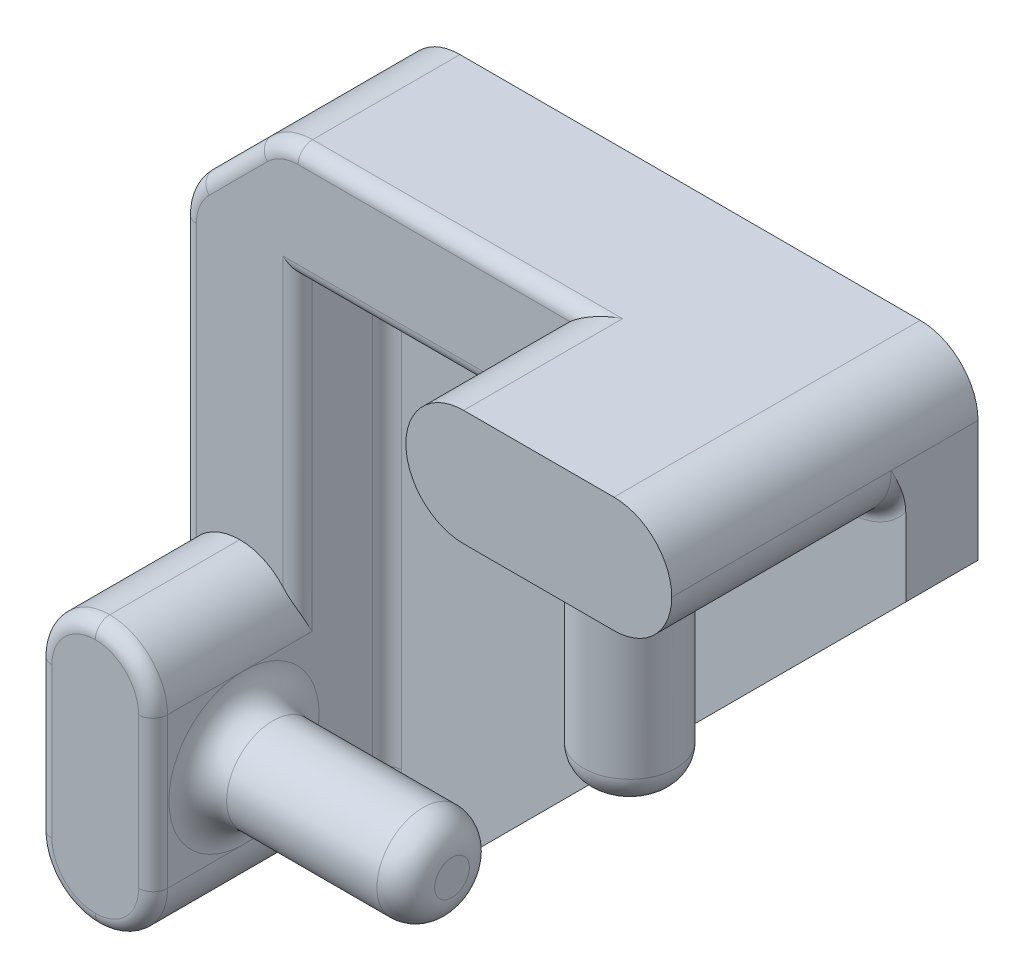
SolidWorks part; units mm, degrees
ref_plane "Plano frontal" through (0, 0, 0) normal (0, 0, 1) x (1, 0, 0)
ref_plane "Plano superior" through (0, 0, 0) normal (0, 1, 0) x (1, 0, 0)
ref_plane "Plano direito" through (0, 0, 0) normal (1, 0, 0) x (0, 0, -1)
sketch "Esboço1" plane through (0, 0, 0) normal (0, 0, 1) x (1, 0, 0)
  line L107 (-13.25, 6.5637) -> (-13.25, -11.25)
  line L117 (-11.25, -13.25) -> (-2.5074, -13.25)
  line L118 (-2.5074, -13.25) -> (13.25, 2.5074)
  line L119 (13.25, 2.5074) -> (13.25, 11.25)
  line L129 (11.25, 13.25) -> (-6.5637, 13.25)
  line L135 (-7.9779, 12.6642) -> (-12.6642, 7.9779)
  circle A0 centre (0, 0) radius 1.7
  arc A1 (13.25, 11.25) -> (11.25, 13.25) centre (11.25, 11.25) ccw
  arc A2 (-6.5637, 13.25) -> (-7.9779, 12.6642) centre (-6.5637, 11.25) ccw
  arc A3 (-12.6642, 7.9779) -> (-13.25, 6.5637) centre (-11.25, 6.5637) ccw
  arc A4 (-13.25, -11.25) -> (-11.25, -13.25) centre (-11.25, -11.25) ccw
  point P23 (-13.25, -13.25)
  dimension "D1" = 3.4
  dimension "D7" = 2
  dimension "D2" = 7.5962
  dimension "D3" = 135
  dimension "D4" = 22.1924
  dimension "D5" = 26.5
  dimension "D6" = 26.5
  dimension "D8" = 10.7426
  dimension "D9" = 13.25
extrude "Ressalto-extrusão1" add sketch "Esboço1" along normal blind 2.5 contours L135 L107 A1 A2 L117 L118 L119 A3 A4 L129 A0 region at (-1.4497, 1.4497, 0)
ref_plane "Plano1" through (0, 0, 2.5) normal (0, 0, -1) x (-1, 0, 0)
sketch "Esboço5" plane through (0, 0, 2.5) normal (0, 0, -1) x (-1, 0, 0)
  line L0 (-11.25, 4.7) -> (4.7, 4.7)
  line L1 (11.25, -13.25) -> (2.5074, -13.25) construction
  line L2 (4.7, 4.7) -> (4.7, -11.25)
  line L3 (-13.25, 2.5074) -> (-13.25, 11.25) construction
  line L4 (-11.25, 13.25) -> (6.5637, 13.25) construction
  line L5 (13.25, 6.5637) -> (13.25, -11.25) construction
  line L6 (7.9779, 12.6642) -> (12.6642, 7.9779) construction
  line L7 (-13.25, 6.7) -> (-13.25, 11.25)
  line L8 (-11.25, 13.25) -> (6.5637, 13.25)
  line L9 (7.9779, 12.6642) -> (12.6642, 7.9779)
  line L10 (13.25, 6.5637) -> (13.25, -11.25)
  line L11 (11.25, -13.25) -> (6.7, -13.25)
  arc A0 (7.9779, 12.6642) -> (6.5637, 13.25) centre (6.5637, 11.25) ccw construction
  arc A1 (11.25, -13.25) -> (13.25, -11.25) centre (11.25, -11.25) ccw
  arc A2 (13.25, 6.5637) -> (12.6642, 7.9779) centre (11.25, 6.5637) ccw
  arc A3 (7.9779, 12.6642) -> (6.5637, 13.25) centre (6.5637, 11.25) ccw
  arc A8 (4.7, -11.25) -> (6.7, -13.25) centre (6.7, -11.25) ccw
  arc A9 (-11.25, 4.7) -> (-13.25, 6.7) centre (-11.25, 6.7) cw
  arc A10 (-11.25, 13.25) -> (-13.25, 11.25) centre (-11.25, 11.25) ccw
  point P19 (4.7, -13.25)
  point P22 (-13.25, 4.7)
  dimension "D3" = 2
  dimension "D1" = 8.55
  dimension "D2" = 8.55
extrude "Ressalto-extrusão3" add sketch "Esboço5" against normal blind 3.1
sketch "Esboço6" plane through (0, 0, 5.6) normal (0, 0, 1) x (1, 0, 0)
  line L0 (-6.7, -4.05) -> (-11.25, -4.05)
  line L1 (-4.7, 4.7) -> (-4.7, -11.25) construction
  line L2 (-13.25, -11.25) -> (-13.25, 6.5637) construction
  line L3 (-6.7, -13.25) -> (-11.25, -13.25) construction
  line L4 (4.05, 6.7) -> (4.05, 11.25)
  line L5 (11.25, 4.7) -> (-4.7, 4.7) construction
  line L6 (-6.5637, 13.25) -> (11.25, 13.25) construction
  line L7 (13.25, 11.25) -> (13.25, 6.7) construction
  line L15 (-4.7, -11.25) -> (-4.7, 4.7)
  line L16 (-4.7, 4.7) -> (11.25, 4.7)
  line L17 (13.25, 6.7) -> (13.25, 11.25)
  line L18 (11.25, 13.25) -> (-6.5637, 13.25)
  line L19 (-7.9779, 12.6642) -> (-12.6642, 7.9779)
  line L20 (-13.25, 6.5637) -> (-13.25, -11.25)
  line L21 (-11.25, -13.25) -> (-6.7, -13.25)
  line L22 (-4.7, -11.25) -> (-4.7, -6.05)
  line L23 (6.05, 4.7) -> (11.25, 4.7)
  line L24 (13.25, 6.7) -> (13.25, 11.25)
  line L25 (11.25, 13.25) -> (6.05, 13.25)
  line L27 (-13.25, -6.05) -> (-13.25, -11.25)
  line L28 (-11.25, -13.25) -> (-6.7, -13.25)
  arc A0 (4.05, 11.25) -> (6.05, 13.25) centre (6.05, 11.25) cw
  arc A1 (4.05, 6.7) -> (6.05, 4.7) centre (6.05, 6.7) ccw
  arc A2 (-6.7, -4.05) -> (-4.7, -6.05) centre (-6.7, -6.05) cw
  arc A3 (-11.25, -4.05) -> (-13.25, -6.05) centre (-11.25, -6.05) ccw
  arc A6 (11.25, 4.7) -> (13.25, 6.7) centre (11.25, 6.7) ccw
  arc A7 (13.25, 11.25) -> (11.25, 13.25) centre (11.25, 11.25) ccw
  arc A8 (-6.5637, 13.25) -> (-7.9779, 12.6642) centre (-6.5637, 11.25) ccw
  arc A9 (-12.6642, 7.9779) -> (-13.25, 6.5637) centre (-11.25, 6.5637) ccw
  arc A10 (-13.25, -11.25) -> (-11.25, -13.25) centre (-11.25, -11.25) ccw
  arc A11 (-6.7, -13.25) -> (-4.7, -11.25) centre (-6.7, -11.25) ccw
  arc A12 (11.25, 4.7) -> (13.25, 6.7) centre (11.25, 6.7) ccw
  arc A13 (13.25, 11.25) -> (11.25, 13.25) centre (11.25, 11.25) ccw
  arc A16 (-13.25, -11.25) -> (-11.25, -13.25) centre (-11.25, -11.25) ccw
  arc A17 (-6.7, -13.25) -> (-4.7, -11.25) centre (-6.7, -11.25) ccw
  point P23 (4.05, 13.25)
  point P32 (4.05, 4.7)
  point P43 (-4.7, -4.05)
  point P46 (-13.25, -4.05)
  dimension "D4" = 2
  dimension "D1" = 9.2
  dimension "D2" = 9.2
  dimension "D3" = 0
extrude "Ressalto-extrusão4" add sketch "Esboço6" along normal blind 5
sketch "Esboço7" plane through (-4.7, 0, 0) normal (1, 0, 0) x (0, 0, -1)
  line L0 (-2.5, -8.65) -> (-5.854, -8.65) construction
  line L3 (-2.5, 4.7) -> (-2.5, -11.25) construction
  circle A0 centre (-7.454, -8.65) radius 1.6
  dimension "D1" = 3.2
  dimension "D2" = 3.354
extrude "Corte-extrusão3" [suppressed] cut sketch "Esboço7" against normal through all
ref_plane "Plano2" through (0, 0, 0) normal (-0.7071, -0.7071, 0) x (-0.7071, 0.7071, 0)
mirror "Espelhar1" [suppressed] about plane through (0, 0, 0) normal (-0.7071, -0.7071, 0)
sketch "Esboço11" plane through (0, 0, 5.6) normal (0, 0, 1) x (1, 0, 0)
  line L61 (-8.7, -13.25) -> (-8.7, 4.679)
  line L62 (-8.1142, 6.0932) -> (-6.0932, 8.1142)
  line L63 (-4.679, 8.7) -> (13.25, 8.7)
  line L64 (-12.6642, 7.9779) -> (-7.9779, 12.6642) construction
  line L67 (-11.25, -13.25) -> (-6.7, -13.25) construction
  line L68 (13.25, 6.7) -> (13.25, 11.25) construction
  line L69 (13.25, 8.7) -> (13.25, 14.8842)
  line L70 (13.25, 14.8842) -> (-15.6971, 14.8842)
  line L71 (-15.6971, 14.8842) -> (-15.6971, -13.25)
  line L72 (-15.6971, -13.25) -> (-8.7, -13.25)
  line L73 (-4.7, 4.7) -> (-4.7, -6.05) construction
  line L74 (6.05, 4.7) -> (-4.7, 4.7) construction
  arc A28 (-6.0932, 8.1142) -> (-4.679, 8.7) centre (-4.679, 6.7) cw
  arc A29 (-8.7, 4.679) -> (-8.1142, 6.0932) centre (-6.7, 4.679) cw
  dimension "D4" = 2
  dimension "D1" = 4
  dimension "D2" = 4
  dimension "D3" = 4.55
extrude "Corte-extrusão5" cut sketch "Esboço11" against normal through all both and the other way through all
fillet "Filete5" radius 2 4 edges at (4.05, 8.7, 8.1) (-8.7, -4.05, 8.1) (-8.7, -13.25, 5.3) (13.25, 8.7, 5.3)
fillet "Filete3" radius 0.5 17 edges at (12.6642, 5.2858, 2.5) (-5.2858, -12.6642, 2.5) (-5.2858, -12.6642, 10.6) (-5.2858, -4.6358, 10.6) (3.275, 4.7, 2.5) (-4.7, -3.275, 2.5) (-4.7, -0.675, 5.6) (0.675, 4.7, 5.6) (-4.7, -8.65, 10.6) (-8.1142, -12.6642, 10.6) (-8.7, -8.65, 10.6) (-8.1142, -4.6358, 10.6) (0.6855, 8.7, 5.6) (-5.4444, 8.5478, 5.6) (-7.1037, 7.1037, 5.6) (-8.5478, 5.4444, 5.6) (-8.7, -0.6855, 5.6)
ref_plane "Plano3" through (-6.7, 0, 0) normal (1, 0, 0) x (0, 0, -1)
sketch "Esboço10" [suppressed] plane through (-8.975, 0, 0) normal (1, 0, 0) x (0, 0, -1)
  line L0 (-9.0994, -5.8) -> (-13.6026, -5.8)
  line L1 (-4.1631, -8.65) -> (-5.8086, -5.8)
  line L2 (-5.8086, -5.8) -> (-9.0994, -5.8)
  line L3 (-9.0994, -5.8) -> (-10.7449, -8.65) construction
  line L4 (-10.7449, -8.65) -> (-9.0994, -11.5) construction
  line L5 (-9.0994, -11.5) -> (-5.8086, -11.5)
  line L6 (-5.8086, -11.5) -> (-4.1631, -8.65)
  line L7 (-13.6026, -5.8) -> (-13.6026, -11.5)
  line L8 (-13.6026, -11.5) -> (-9.0994, -11.5)
  circle A0 centre (-7.454, -8.65) radius 2.85 construction
  dimension "D1" = 5.7
  dimension "D2" = 4.5031
extrude "Corte-extrusão4" [suppressed] cut sketch "Esboço10" against normal mid plane 2.7
mirror "Espelhar2" [suppressed] about plane through (0, 0, 0) normal (-0.7071, -0.7071, 0)
extrude "Ressalto-extrusão5" add sketch "Esboço7<2>" along normal blind 7.2
sketch "Esboço7<2>" plane through (-4.7, 0, 0) normal (1, 0, 0) x (0, 0, -1) same geometry as "Esboço7"
mirror "Espelhar3" about plane through (0, 0, 0) normal (-0.7071, -0.7071, 0) of "Ressalto-extrusão5"
fillet "Filete4" radius 1 4 edges at (8.65, -2.5, 5.854) (2.5, -8.65, 5.854) (8.65, 4.7, 5.854) (-4.7, -8.65, 5.854)
